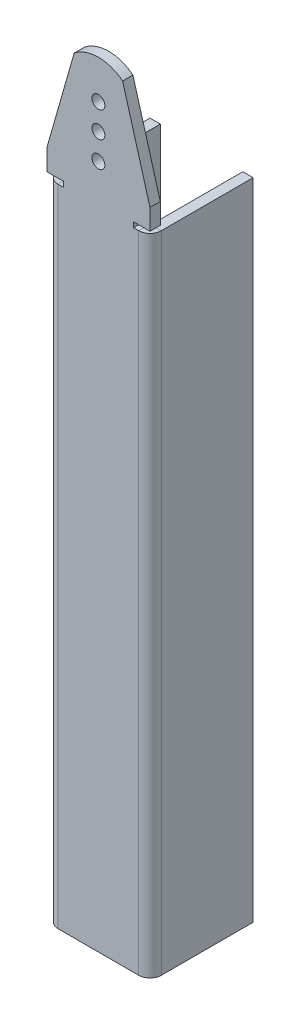
SolidWorks part; units mm, degrees
note: The reader was unsure of these and kept them because the rebuilt part matched: flange length of "边线-法兰4", "边线-法兰8".
ref_plane "前视基准面" through (0, 0, 0) normal (0, 0, 1) x (1, 0, 0)
ref_plane "上视基准面" through (0, 0, 0) normal (0, 1, 0) x (1, 0, 0)
ref_plane "右视基准面" through (0, 0, 0) normal (1, 0, 0) x (0, 0, -1)
sketch "草图1" plane through (0, 0, 0) normal (0, 0, 1) x (1, 0, 0)
  line L1 (0, 0) -> (80, 0)
  line L2 (0, 0) -> (0, 520.0543)
  line L4 (80, 0) -> (80, 520)
  line L8 (0, 520.0543) -> (21.21, 594.2774)
  line L9 (58.758, 594.2774) -> (80, 520)
  arc A1 (21.21, 594.2774) -> (58.758, 594.2774) centre (39.984, 570.8779) cw
  circle A2 centre (39.984, 570.8779) radius 5
  circle A3 centre (39.984, 550.8779) radius 5
  circle A4 centre (39.984, 530.8779) radius 5
  point P8 (39.984, 600.8779)
  dimension "D3" = 3
  dimension "D6" = 10
  dimension "D1" = 520
  dimension "D2" = 80
  dimension "D4" = 600.8779
  dimension "D5" = 20
ref_plane "基准面2" through (80, 0, 0) normal (1, 0, 0) x (0, 0, -1)
base flange "基体-法兰2" sketch "草图1" thickness 8 reverse thickness direction no parameters "D1"=0.7366
edge flange "边线-法兰4" sketch "草图36" flange angle 90 flange length 80 flange position material inside bend radius 0.7366 thickness 8 relief rectangular parameters "D6"=10
sketch "草图36" plane through (0, 0, -8) normal (1, 0, 0) x (0, -1, 0)
  line L0 (0, 0) -> (-520, 0) construction
  line L2 (-500, 0) -> (-500, 72)
  line L3 (-500, 72) -> (0, 72)
  line L4 (0, 72) -> (0, 0)
  line L5 (0, 0) -> (-520.0543, 0) construction
  line L6 (0, 0) -> (-500, 0)
bend "边线折弯4" bend radius 0.7366 bend angle 90 parameters "D5"=1
edge flange "边线-法兰8" sketch "草图48" flange angle 90 flange length 80 flange position material inside bend radius 0.7366 thickness 8 relief rectangular parameters "D6"=10
sketch "草图48" plane through (80, 0, -8) normal (-1, 0, 0) x (0, 1, 0)
  line L2 (0, 0) -> (0, 72)
  line L3 (0, 72) -> (500, 72)
  line L4 (500, 72) -> (500, 0)
  line L22 (500, 0) -> (0, 0)
bend "边线折弯8" bend radius 0.7366 bend angle 90 parameters "D5"=2
sketch "草图49" plane through (0, 0, 0) normal (0, -1, 0) x (1, 0, 0)
  line L30 (80, 0) -> (80, -80) construction
  line L31 (93.8273, -40) -> (-32.2739, -40) construction
  line L32 (8, 10) -> (-22.0281, 10)
  line L33 (-22.0281, 10) -> (-22.0281, -90)
  line L39 (8, -90) -> (8, 10)
  line L40 (8, -8.7366) -> (8, -80) construction
  line L41 (8.7366, 0) -> (71.2634, 0) construction
  line L42 (-9.1169, 7) -> (-9.1169, 3)
  line L46 (-9.1169, 7) -> (-5.1169, 7)
  line L47 (-5.1169, 7) -> (-5.1169, 3)
  line L48 (-5.1169, 3) -> (-9.1169, 3)
  line L49 (-5.1169, -83) -> (-9.1169, -83)
  line L50 (-5.1169, -87) -> (-5.1169, -83)
  line L51 (-9.1169, -87) -> (-5.1169, -87)
  line L52 (-9.1169, -87) -> (-9.1169, -83)
  line L53 (8, -90) -> (-22.0281, -90)
  line L54 (40, 17.2719) -> (40, -98.8374) construction
  line L55 (85.1169, -87) -> (85.1169, -83)
  line L56 (89.1169, -87) -> (85.1169, -87)
  line L57 (89.1169, -87) -> (89.1169, -83)
  line L58 (85.1169, -83) -> (89.1169, -83)
  line L59 (85.1169, 7) -> (85.1169, 3)
  line L60 (89.1169, 7) -> (85.1169, 7)
  line L61 (89.1169, 7) -> (89.1169, 3)
  line L62 (85.1169, 3) -> (89.1169, 3)
  line L63 (72, -90) -> (102.0281, -90)
  line L64 (102.0281, 10) -> (102.0281, -90)
  line L65 (72, 10) -> (102.0281, 10)
  line L66 (72, -90) -> (72, 10)
  point P21 (8, -40)
  point P22 (-22.0281, -40)
  dimension "D1" = 10
ref_plane "基准面4" through (8, 0, -8.7366) normal (0, 0, -1) x (-1, 0, 0)
sketch "草图50" plane through (0, 0, 0) normal (0, -1, 0) x (1, 0, 0)
  line L0 (0, 0) -> (0, -80)
  line L1 (80, -80) -> (80, -8.7366) construction
  line L2 (0, -40) -> (80, -40) construction
  line L3 (8.7366, 0) -> (71.2634, 0) construction
  line L5 (40, 0) -> (40, -80) construction
  circle A0 centre (40, -40) radius 7.5
sketch "折弯-线3" [suppressed] plane through (0, 0, 0) normal (0, 1, 0) x (1, 0, 0)
sketch "边界框3" [suppressed] plane through (0, 0, 0) normal (0, 1, 0) x (1, 0, 0)
sheet metal parameters "钣金7" thickness 8 parameters "D1"=0.7366
flat pattern "平展型式7" [suppressed]
sketch "折弯-线4" plane through (0, 0, 0) normal (0, 1, 0) x (1, 0, 0)
sketch3d "边界框4" [suppressed]
  line L0 (40.016, -570.8779, 0) -> (40.016, 30, 0) construction
  line L1 (-39.984, -570.8779, 0) -> (-39.984, 30, 0) construction
  line L2 (40.016, -570.8779, 0) -> (-39.984, -570.8779, 0) construction
  line L3 (40.016, 30, 0) -> (-39.984, 30, 0) construction
sheet metal parameters "钣金12" thickness 8 parameters "D1"=0.7366
flat pattern "平展型式7"
sketch "折弯-线4" plane through (0, 0, 0) normal (0, 0, 1) x (1, 0, 0)
  line L0 (5.0165, 500) -> (5.0165, 0) construction
  line L1 (5.0165, 500) -> (5.0165, 0) construction
sketch3d "边界框4" [suppressed]
  line L0 (40.016, -570.8779, 0) -> (40.016, 30, 0) construction
  line L1 (-109.951, -570.8779, 0) -> (-109.951, 30, 0) construction
  line L2 (40.016, -570.8779, 0) -> (-109.951, -570.8779, 0) construction
  line L3 (40.016, 30, 0) -> (-109.951, 30, 0) construction
bend of the flat pattern "展平-<边线折弯4>1"
sheet metal parameters "钣金16" thickness 8 parameters "D1"=0.7366
flat pattern "平展型式7"
sketch "折弯-线4" plane through (0, 0, 0) normal (0, 0, 1) x (1, 0, 0)
  line L0 (5.0165, 500) -> (5.0165, 0) construction
  line L1 (5.0165, 500) -> (5.0165, 0) construction
  line L2 (74.9835, 0) -> (74.9835, 500) construction
  line L3 (74.9835, 0) -> (74.9835, 500) construction
sketch3d "边界框4" [suppressed]
  line L0 (109.983, -570.8779, 0) -> (109.983, 30, 0) construction
  line L1 (-109.951, -570.8779, 0) -> (-109.951, 30, 0) construction
  line L2 (109.983, -570.8779, 0) -> (-109.951, -570.8779, 0) construction
  line L3 (109.983, 30, 0) -> (-109.951, 30, 0) construction
bend of the flat pattern "展平-<边线折弯4>1"
bend of the flat pattern "展平-<边线折弯8>1"
